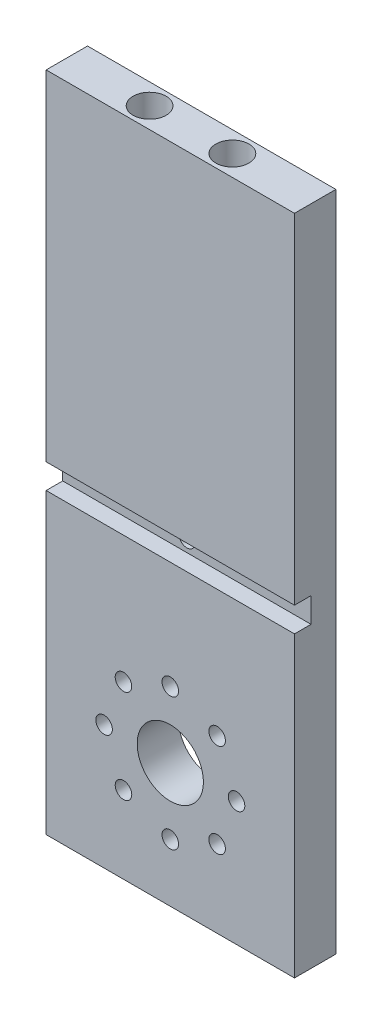
SolidWorks part; units mm, degrees
material "1060 Alloy"
ref_plane "Front Plane" through (0, 0, 0) normal (0, 0, 1) x (1, 0, 0)
ref_plane "Top Plane" through (0, 0, 0) normal (0, 1, 0) x (1, 0, 0)
ref_plane "Right Plane" through (0, 0, 0) normal (1, 0, 0) x (0, 0, -1)
sketch "Sketch1" plane through (0, 0, 0) normal (0, 1, 0) x (1, 0, 0)
  line L1 (-15, 2.5) -> (15, 2.5)
  line L2 (-15, 2.5) -> (-15, -2.5)
  line L3 (-15, -2.5) -> (15, -2.5)
  line L4 (15, 2.5) -> (15, -2.5)
  line L5 (-15, 2.5) -> (15, -2.5) construction
  line L6 (-15, -2.5) -> (15, 2.5) construction
  point P0 (0, 0)
  dimension "D1" = 5
  dimension "D2" = 30
extrude "Boss-Extrude1" add sketch "Sketch1" along normal blind 80 contours L1 L4 L3 L2
sketch "Sketch2" plane through (0, 80, 0) normal (0, 1, 0) x (1, 0, 0)
  line L0 (-5, 0) -> (5, 0) construction
  line L3 (0, 2.5) -> (0, -2.5) construction
  line L4 (-15, 2.5) -> (15, 2.5) construction
  line L5 (-15, -2.5) -> (15, -2.5) construction
  circle A0 centre (-5, 0) radius 2
  circle A1 centre (5, 0) radius 2
  point P10 (0, 0)
  dimension "D1" = 4
  dimension "D2" = 4
  dimension "D3" = 10
extrude "Cut-Extrude1" cut sketch "Sketch2" against normal blind 10
sketch "Sketch3" plane through (0, 0, 2.5) normal (0, 0, 1) x (1, 0, 0)
  line L0 (0, 80) -> (0, 0) construction
  line L1 (-15, 80) -> (15, 80) construction
  line L2 (-15, 0) -> (15, 0) construction
  line L6 (15, 80) -> (15, 0) construction
  circle A6 centre (0, 15) radius 8
  circle A7 centre (0, 23) radius 1
  circle A8 centre (5.6569, 20.6569) radius 1
  circle A9 centre (0, 15) radius 8
  circle A10 centre (8, 15) radius 1
  circle A11 centre (0, 15) radius 8
  circle A12 centre (5.6569, 9.3431) radius 1
  circle A13 centre (0, 15) radius 8
  circle A14 centre (0, 7) radius 1
  circle A15 centre (0, 15) radius 8
  circle A16 centre (-5.6569, 9.3431) radius 1
  circle A17 centre (0, 15) radius 8
  circle A18 centre (-8, 15) radius 1
  circle A19 centre (0, 15) radius 8
  circle A20 centre (-5.6569, 20.6569) radius 1
  circle A21 centre (0, 15) radius 8
  circle A22 centre (0, 15) radius 4
  point P47 (0, 15)
  dimension "D1" = 16
  dimension "D2" = 15
  dimension "D3" = 15
  dimension "D8" = 2
  dimension "D10" = 8
  dimension "D9" = 8
sketch "Sketch4" plane through (0, 0, 2.5) normal (0, 0, 1) x (1, 0, 0)
  line L0 (0, 80) -> (0, 0) construction
  circle A0 centre (0, 30) radius 1
  circle A1 centre (0, 0) radius 1
  dimension "D1" = 2
  dimension "D2" = 2
  dimension "D3" = 30
  dimension "D4" = 15
extrude "Cut-Extrude3" cut sketch "Sketch3" against normal through all contours A19 A20 | A19 A20 | L0 A7 A21 | A7 L0 A6 | A6 L0 A7 | L0 A21 A7 | A6 A8 | A6 A8 | A9 A10 | A9 A10 | A11 A12 | A11 A12 | A14 L0 A21 | A21 L0 A14 | L0 A13 A14 | L0 A14 A13 | A15 A16 | A15 A16 | A17 A18 | A17 A18 | L0 A22 | A22 L0 region at (0.4328, 23.413, 2.5) region at (-0.4328, 23.413, 2.5) region at (0.4155, 22.5645, 2.5) region at (-0.4155, 22.5645, 2.5) region at (-5.3489, 20.3489, 2.5) region at (-5.9489, 20.9489, 2.5) region at (1.6977, 15, 2.5) region at (-1.6977, 15, 2.5) region at (5.9489, 20.9489, 2.5) region at (5.3489, 20.3489, 2.5) region at (-7.5645, 15, 2.5) region at (-8.413, 15, 2.5) region at (0.4155, 7.4355, 2.5) region at (-0.4155, 7.4355, 2.5) region at (8.413, 15, 2.5) region at (7.5645, 15, 2.5) region at (0.4328, 6.587, 2.5) region at (-0.4328, 6.587, 2.5) region at (-5.3489, 9.6511, 2.5) region at (-5.9489, 9.0511, 2.5) region at (5.3489, 9.6511, 2.5) region at (5.9489, 9.0511, 2.5)
sketch "Sketch5" plane through (0, 0, 2.5) normal (0, 0, 1) x (1, 0, 0)
  line L0 (-15, 80) -> (-15, 0) construction
  line L1 (-15, 39) -> (15, 39)
  line L2 (-15, 39) -> (-15, 36)
  line L3 (-15, 36) -> (15, 36)
  line L4 (15, 39) -> (15, 36)
  line L5 (15, 80) -> (15, 0) construction
  line L6 (-15, 0) -> (15, 0) construction
  dimension "D1" = 39
  dimension "D2" = 3
extrude "Cut-Extrude4" cut sketch "Sketch5" against normal blind 2
sketch "Sketch6" plane through (0, 0, 0.5) normal (0, 0, 1) x (1, 0, 0)
  line L0 (-15, 37.5) -> (15, 37.5) construction
  line L1 (-15, 39) -> (-15, 36) construction
  line L2 (15, 36) -> (15, 39) construction
  line L3 (0, 39) -> (0, 36) construction
  line L4 (15, 39) -> (-15, 39) construction
  line L5 (-15, 36) -> (15, 36) construction
  circle A0 centre (0, 37.5) radius 1
  dimension "D1" = 2
extrude "Cut-Extrude5" cut sketch "Sketch6" against normal through all contours A0
